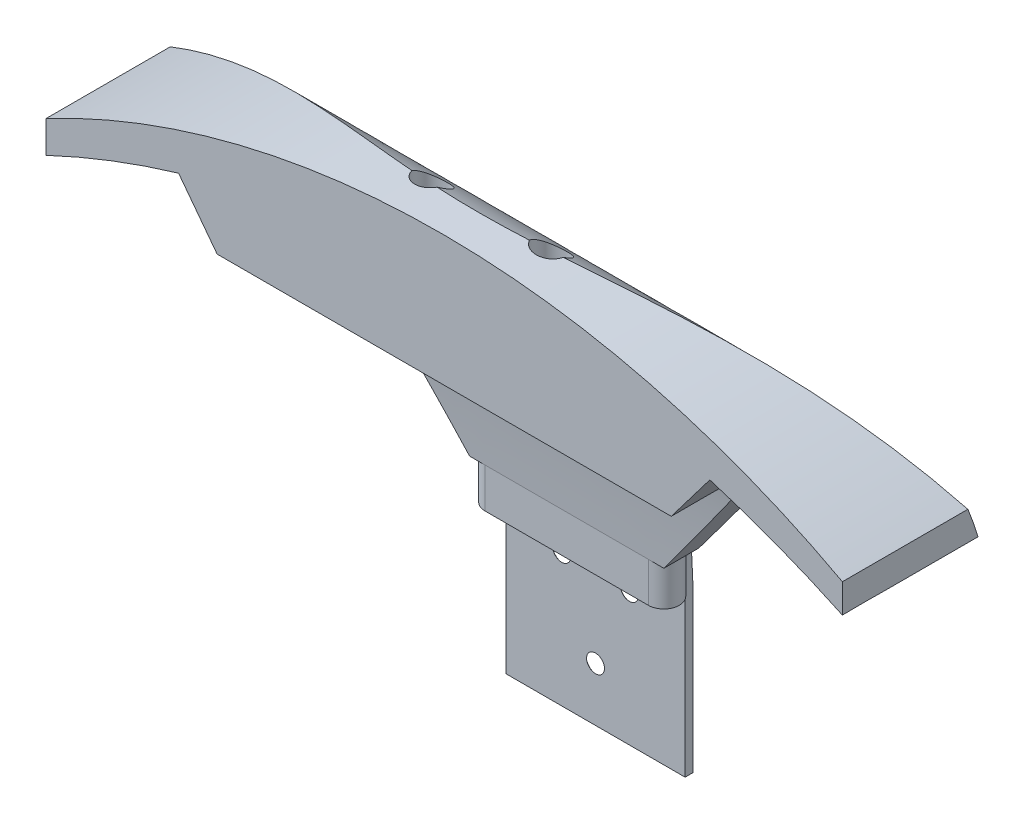
SolidWorks part; units mm, degrees
ref_plane "Front Plane" through (0, 0, 0) normal (0, 0, 1) x (1, 0, 0)
ref_plane "Top Plane" through (0, 0, 0) normal (0, 1, 0) x (1, 0, 0)
ref_plane "Right Plane" through (0, 0, 0) normal (1, 0, 0) x (0, 0, -1)
sketch "Sketch1" plane through (0, 0, 0) normal (0, 1, 0) x (1, 0, 0)
  line L1 (-22.5, -20) -> (22.5, -20)
  line L2 (-22.5, -20) -> (-22.5, 20)
  line L3 (-22.5, 20) -> (22.5, 20)
  line L4 (22.5, -20) -> (22.5, 20)
  line L5 (-22.5, -20) -> (22.5, 20) construction
  line L6 (-22.5, 20) -> (22.5, -20) construction
  point P0 (0, 0)
  dimension "D1" = 40
  dimension "D2" = 45
extrude "Boss-Extrude1" add sketch "Sketch1" along normal blind 2
sketch "Sketch2" plane through (0, 0, -20) normal (0, 0, -1) x (-1, 0, 0)
  line L0 (0, 0) -> (0, 9.0586) construction
  line L1 (-22.5, 0) -> (22.5, 0) construction
  line L2 (-20.5, 9.2325) -> (20.5, 9.2325)
  line L3 (-22.5, 2) -> (-22.5, 0)
  line L4 (-22.5, 0) -> (22.5, 0)
  line L5 (22.5, 0) -> (22.5, 2)
  arc A2 (-20.5, 9.2325) -> (-22.5, 2) centre (-20.5, 5.3397) ccw
  arc A3 (22.5, 2) -> (20.5, 9.2325) centre (20.5, 5.3397) ccw
extrude "Boss-Extrude2" add sketch "Sketch2" along normal blind 10
sketch "Sketch3" plane through (0, 0, -30) normal (0, 0, -1) x (-1, 0, 0)
  line L1 (-20.5, 0.0025) -> (20.5, 0.0025)
  line L2 (-20.5, 0.0025) -> (-20.5, 9.2325)
  line L3 (-20.5, 9.2325) -> (20.5, 9.2325)
  line L4 (20.5, 0.0025) -> (20.5, 9.2325)
  line L5 (-20.5, 0.0025) -> (20.5, 9.2325) construction
  line L6 (-20.5, 9.2325) -> (20.5, 0.0025) construction
  point P0 (0, 4.6175)
  dimension "D1" = 4.615
  dimension "D2" = 0
extrude "Boss-Extrude3" add sketch "Sketch3" along normal blind 45
sketch "Sketch4" plane through (0, 0, -75) normal (0, 0, -1) x (-1, 0, 0)
  line L0 (-20.5, 0.0025) -> (20.5, 0.0025)
  line L1 (-20.5, 0.0025) -> (-20.5, 40.0025)
  line L2 (20.5, 0.0025) -> (20.5, 40.0025)
  line L3 (-20.5, 40.0025) -> (20.5, 40.0025)
  line L4 (0, 0) -> (0, 45.7769) construction
  circle A0 centre (-15, 35.0025) radius 2
  circle A1 centre (15, 35.0025) radius 2
  dimension "D2" = 30
  dimension "D3" = 35
  dimension "D4" = 4
  dimension "D1" = 40
extrude "Boss-Extrude4" add sketch "Sketch4" along normal blind 34
sketch "Sketch6" plane through (0, 9.2325, 0) normal (0, 1, 0) x (1, 0, 0)
  line L1 (-20.5, 75) -> (20.5, 75)
  line L2 (-20.5, 75) -> (-20.5, 30)
  line L3 (-20.5, 30) -> (20.5, 30)
  line L4 (20.5, 75) -> (20.5, 30)
extrude "Boss-Extrude5" add sketch "Sketch6" along normal up to vertex (30.77 mm away) up to point (-20.5, 40.0025, -75)
sketch "Sketch9" plane through (0, 0, 0) normal (1, 0, 0) x (0, 0, -1)
  line L1 (30, 40.0025) -> (109, 40.0025)
  line L2 (30, 40.0025) -> (30, 0.0025)
  line L3 (30, 0.0025) -> (109, 0.0025)
  line L4 (109, 40.0025) -> (109, 0.0025)
extrude "Boss-Extrude6" add sketch "Sketch9" along normal mid plane 200
sketch "Sketch10" plane through (0, 0, -30) normal (0, 0, 1) x (1, 0, 0)
  line L0 (0, 0) -> (0, 53.138) construction
  circle A0 centre (-15, 28.162) radius 2
  circle A1 centre (15, 28.162) radius 2
  dimension "D1" = 30
  dimension "D2" = 4
extrude "Cut-Extrude4" cut sketch "Sketch10" against normal through all
sketch "Sketch15" plane through (0, 0, -109) normal (0, 0, -1) x (-1, 0, 0)
  circle A0 centre (15, 28.162) radius 4
  circle A1 centre (-15, 28.162) radius 4
  dimension "D1" = 8
  dimension "D2" = 8
extrude "Cut-Extrude9" cut sketch "Sketch15" against normal blind 32
sketch "Sketch7" plane through (0, 0, 0) normal (1, 0, 0) x (0, 0, -1)
  line L0 (20, 2) -> (20, -8.9346) construction
  line L1 (-20, 0) -> (30, 0) construction
  line L4 (20, 0) -> (20, -8.9346)
  line L5 (20, -8.9346) -> (79, -8.9346)
  line L9 (89.1717, -8.9346) -> (79, -8.9346)
  line L10 (109, 40.0025) -> (121.5433, 40.0025)
  line L11 (121.5433, 40.0025) -> (121.5433, -8.9346)
  line L12 (121.5433, -8.9346) -> (89.1717, -8.9346)
  spline S0 degree 3 poles (20, 0) (42.8971, 1.5797) (98.6703, -1.8271) (109, 40.0025) knots 0 0 0 0 1 1 1 1
extrude "Cut-Extrude6" cut sketch "Sketch7" against normal mid plane 250
sketch "Sketch11" plane through (0, 0, 0) normal (1, 0, 0) x (0, 0, -1)
  line L0 (30, 9.2325) -> (8.5549, 9.2325)
  line L1 (109, 40.0025) -> (30, 40.0025) construction
  line L2 (8.5549, 9.2325) -> (8.5549, 44.8463)
  line L3 (8.5549, 44.8463) -> (73, 44.8463)
  line L4 (73, 44.8463) -> (73, 40.0025)
  spline S0 degree 3 poles (30, 9.2325) (63.8873, 12.1315) (70.9315, 16.175) (73.2607, 23.1823) (73, 40.0025) knots 0 0 0 0 0.671043 1 1 1 1
  dimension "D1" = 43
extrude "Cut-Extrude5" cut sketch "Sketch11" against normal mid plane 250
ref_plane "Plane1" through (0, 0, -72) normal (0, 0, 1) x (1, 0, 0)
sketch "Sketch17" plane through (0, 0, -72) normal (0, 0, 1) x (1, 0, 0)
  circle A0 centre (-15, 28.162) radius 4.75
  circle A1 centre (15, 28.162) radius 4.75
  dimension "D1" = 9.5
  dimension "D2" = 9.5
extrude "Cut-Extrude11" cut sketch "Sketch17" against normal blind 3
sketch "Sketch13" plane through (0, 0, 0) normal (0, 1, 0) x (1, 0, 0)
  line L0 (-100, 109) -> (-100, 73) construction
  line L1 (100, 109) -> (100, 73) construction
  line L2 (-100, 81) -> (-129.4744, 81)
  line L3 (-129.4744, 81) -> (-129.4744, 121.5786)
  line L4 (-129.4744, 121.5786) -> (107.7668, 121.5786)
  line L5 (107.7668, 121.5786) -> (107.7668, 80.2671)
  line L6 (107.7668, 80.2671) -> (100, 80.2671)
  arc A0 (-100, 81) -> (100, 80.2671) centre (-0.6859, -106.536) cw
  dimension "D1" = 8
extrude "Cut-Extrude7" cut sketch "Sketch13" along normal through all
sketch "Sketch14" plane through (0, 40.0025, 0) normal (0, 1, 0) x (1, 0, 0)
  line L0 (0, 0) -> (0, 123.6319) construction
  line L2 (-66.7054, 85.7641) -> (-24.3928, 30)
  line L3 (66.7054, 85.7641) -> (24.3928, 30)
  line L4 (-100, 73) -> (-115.9209, 73)
  line L5 (-115.9209, 73) -> (-115.9209, 30)
  line L6 (-115.9209, 30) -> (-24.3928, 30)
  line L7 (24.3928, 30) -> (119.1165, 30)
  line L8 (119.1165, 30) -> (119.1165, 73)
  line L9 (119.1165, 73) -> (100, 73)
  arc A0 (-100, 73) -> (-66.7054, 85.7641) centre (0, -138.0393) cw
  arc A1 (66.7054, 85.7641) -> (100, 73) centre (0, -138.0393) cw
  dimension "D2" = 70
extrude "Cut-Extrude8" cut sketch "Sketch14" against normal through all
sketch "Sketch18" plane through (0, 0, -20) normal (0, 0, 1) x (1, 0, 0)
  circle A0 centre (20.5, 5.3397) radius 1.75
  circle A1 centre (-20.5, 5.3397) radius 1.75
  dimension "D1" = 3.5
  dimension "D2" = 3.5
extrude "Cut-Extrude12" cut sketch "Sketch18" against normal blind 3
sketch "Sketch19" plane through (0, 0, 0) normal (0, -1, 0) x (1, 0, 0)
  line L0 (0, 0) -> (0, 30.8454) construction
  line L1 (-22.5, 20) -> (22.5, 20) construction
  circle A0 centre (-8.5, -13.5) radius 2.25
  circle A1 centre (8.5, -13.5) radius 2.25
  circle A2 centre (0, 6.5) radius 2.25
  dimension "D1" = 4.5
  dimension "D2" = 17
  dimension "D4" = 4.5
  dimension "D3" = 33.5
  dimension "D5" = 13.5
extrude "Cut-Extrude13" cut sketch "Sketch19" against normal through all
fillet "Fillet2" radius 8 3 edges at (-8.5, 0, -15.75) (8.5, 0, -15.75) (0, 0, 4.25)
move or copy body "Body-Move/Copy1" bodies to move or copy 120 copy no rotation origin (0, 19.6159, -42.8815) rotation axis (1, 0, 0) rotation angle 90
